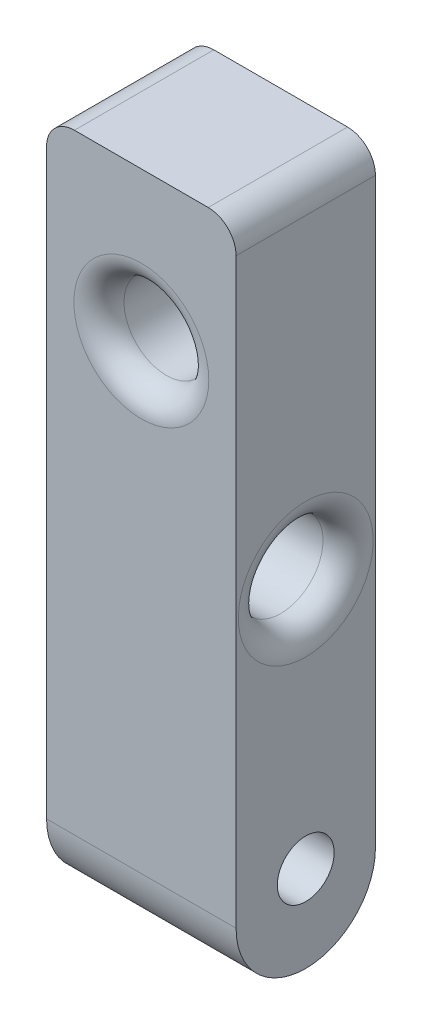
SolidWorks part; units mm, degrees
ref_plane "Front" through (0, 0, 0) normal (0, 0, 1) x (1, 0, 0)
ref_plane "Top" through (0, 0, 0) normal (0, 1, 0) x (1, 0, 0)
ref_plane "Right" through (0, 0, 0) normal (1, 0, 0) x (0, 0, -1)
sketch "Sketch1" plane through (0, 0, 0) normal (0, 0, 1) x (1, 0, 0)
  line L1 (-17, 61) -> (17, 61)
  line L2 (-17, 61) -> (-17, -61)
  line L3 (-17, -61) -> (17, -61)
  line L4 (17, 61) -> (17, -61)
  line L5 (-17, 61) -> (17, -61) construction
  line L6 (-17, -61) -> (17, 61) construction
  circle A0 centre (0, 34.25) radius 7.6
  point P0 (0, 0)
  point P8 (0, -61)
  dimension "D3" = 15.2
  dimension "D1" = 34
  dimension "D2" = 122
  dimension "D4" = 26.75
extrude "Boss-Extrude1" add sketch "Sketch1" along normal blind 25
sketch "Sketch3" plane through (17, 0, 0) normal (1, 0, 0) x (0, 0, -1)
  line L0 (-25, 61) -> (0, 61) construction
  circle A0 centre (-12.5, -0.5) radius 7.6
  circle A1 centre (-12.5, -45.5) radius 5.1
  dimension "D1" = 61.5
  dimension "D2" = 45
  dimension "D3" = 15.2
  dimension "D4" = 10.2
extrude "Cut-Extrude2" cut sketch "Sketch3" against normal through all
sketch "Sketch6" plane through (0, 0, 0) normal (0, 0, -1) x (-1, 0, 0)
  line L0 (17, -61) -> (-17, -61) construction
  circle A0 centre (0, -23) radius 4.1
  dimension "D1" = 38
  dimension "D2" = 8.2
extrude "Cut-Extrude5" cut sketch "Sketch6" against normal blind 18
sketch "Sketch7" plane through (-17, 0, 0) normal (-1, 0, 0) x (0, 0, 1)
  circle A0 centre (12.5, -45.5) radius 11.1
  dimension "D1" = 22.2
extrude "Cut-Extrude6" cut sketch "Sketch7" against normal blind 3.5
sketch "Sketch8" plane through (-13.5, 0, 0) normal (-1, 0, 0) x (0, 0, 1)
  circle A0 centre (12.5, -37.5) radius 1.4
  circle A1 centre (12.5, -45.5) radius 5.1 construction
  circle A2 centre (12.5, -45.5) radius 5.5 construction
  circle A3 centre (20.5, -45.5) radius 1.4
  circle A4 centre (12.5, -53.5) radius 1.4
  circle A5 centre (4.5, -45.5) radius 1.4
  dimension "D1" = 8
  dimension "D3" = 2.8
  dimension "D2" = 4
extrude "Cut-Extrude7" cut sketch "Sketch8" against normal blind 10
fillet "Fillet1" radius 4.5 3 edges at (17, 7.1, 12.5) (-17, 7.1, 12.5) (7.6, 34.25, 25)
fillet "Fillet2" radius 5 2 edges at (17, 61, 12.5) (-17, 61, 12.5)
fillet "Fillet3" 2 edges at (0, -61, 25) (0, -61, 0) type full round first side face at (12.1, 34.25, 25) second side face at (-4.1, -23, 0) middle face at (0, -61, 12.5)
